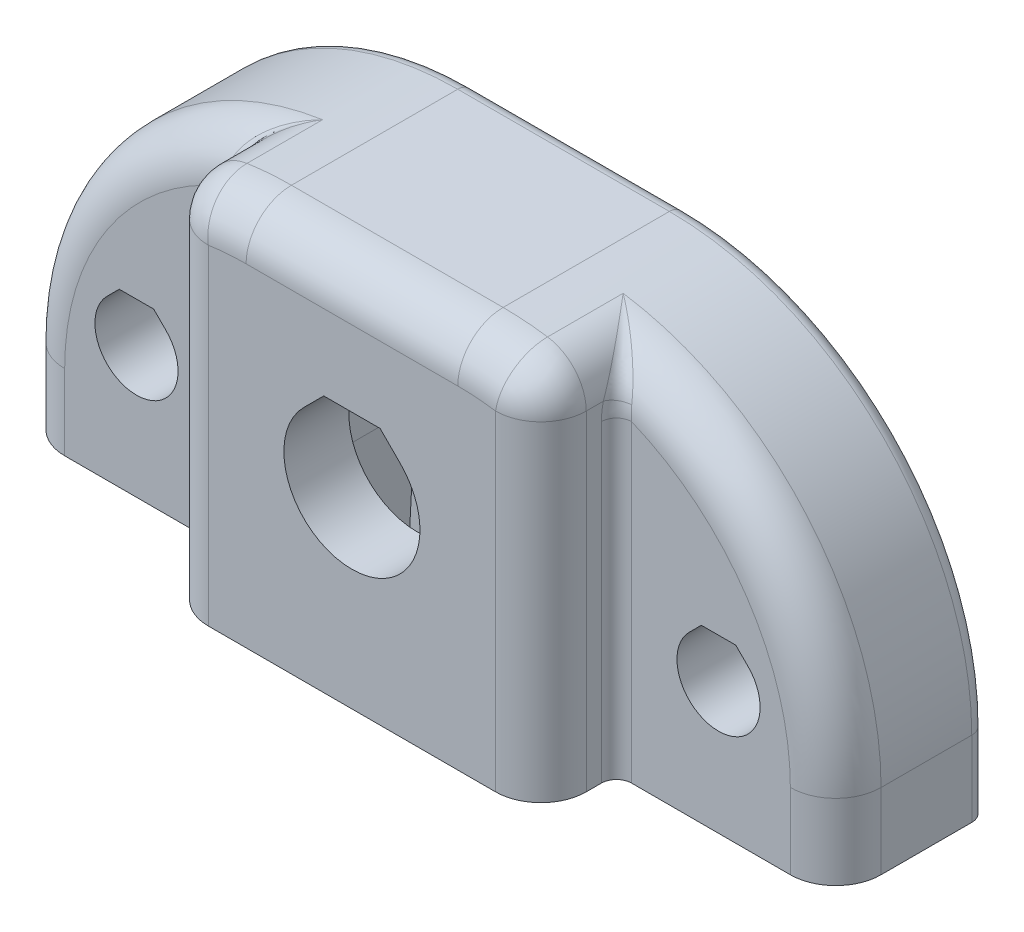
SolidWorks part; units mm, degrees
ref_plane "Front Plane" through (0, 0, 0) normal (0, 0, 1) x (1, 0, 0)
ref_plane "Top Plane" through (0, 0, 0) normal (0, 1, 0) x (1, 0, 0)
ref_plane "Right Plane" through (0, 0, 0) normal (1, 0, 0) x (0, 0, -1)
sketch "Sketch1" plane through (0, 0, 0) normal (0, 0, 1) x (1, 0, 0)
  line L0 (-27, -12.5) -> (27, -12.5)
  line L1 (6.5, 3.7528) -> (0, 7.5056) construction
  line L2 (0, 7.5056) -> (-6.5, 3.7528) construction
  line L3 (-6.5, 3.7528) -> (-6.5, -3.7528) construction
  line L4 (-6.5, -3.7528) -> (0, -7.5056) construction
  line L5 (0, -7.5056) -> (6.5, -3.7528) construction
  line L6 (6.5, -3.7528) -> (6.5, 3.7528) construction
  line L7 (-27, -12.5) -> (-27, -7.5)
  line L8 (27, -12.5) -> (27, -7.5)
  line L9 (-7, 12.5) -> (7, 12.5)
  line L10 (-27, -12.5) -> (27, 12.5) construction
  line L11 (27, -12.5) -> (-27, 12.5) construction
  line L12 (3.182, 3.182) -> (1.864, 4.5)
  line L13 (1.864, 4.5) -> (-1.864, 4.5)
  line L14 (-1.864, 4.5) -> (-3.182, 3.182)
  arc A0 (-3.182, 3.182) -> (3.182, 3.182) centre (0, 0) ccw
  circle A1 centre (0, 0) radius 6.5 construction
  arc A2 (27, -7.5) -> (7, 12.5) centre (7, -7.5) ccw
  arc A3 (-7, 12.5) -> (-27, -7.5) centre (-7, -7.5) ccw
  point P22 (0, 4.5)
  dimension "D1" = 9
  dimension "D2" = 13
  dimension "D5" = 20
  dimension "D3" = 54
  dimension "D4" = 25
  dimension "D6" = 90
extrude "Boss-Extrude1" add sketch "Sketch1" along normal mid plane 15
sketch "Sketch2" plane through (0, 0, 0) normal (0, 0, 1) x (1, 0, 0)
  line L0 (-6.5, -3.7528) -> (-6.9584, -12.5)
  line L1 (0, 7.5056) -> (-6.5, 3.7528)
  line L2 (-6.5, 3.7528) -> (-6.5, -3.7528)
  line L3 (-27, -12.5) -> (27, -12.5) construction
  line L4 (6.5, -3.7528) -> (6.9584, -12.5)
  line L5 (6.5, -3.7528) -> (6.5, 3.7528)
  line L6 (6.5, 3.7528) -> (0, 7.5056)
  line L7 (-6.5, -3.7528) -> (0, -7.5056)
  line L8 (0, -7.5056) -> (6.5, -3.7528)
  line L9 (0, 0) -> (0, -12.5) construction
  line L10 (-6.9584, -12.5) -> (6.9584, -12.5)
  circle A0 centre (0, 0) radius 6.5 construction
  dimension "D1" = 13
  dimension "D2" = 3
  dimension "D3" = 3
  dimension "D4" = 8.7472
extrude "Cut-Extrude1" cut sketch "Sketch2" against normal mid plane 6.4
sketch "Sketch3" plane through (0, 0, 7.5) normal (0, 0, 1) x (1, 0, 0)
  line L0 (12.5, -12.5) -> (12.5, 11.7289)
  line L3 (-27, -12.5) -> (27, -12.5) construction
  line L4 (27, -12.5) -> (27, -7.5) construction
  line L5 (27, -12.5) -> (27, -7.5)
  line L6 (27, -12.5) -> (12.5, -12.5)
  line L7 (6.5, -3.7528) -> (6.5, 3.7528) construction
  line L8 (0, 12.5) -> (0, -12.5) construction
  line L10 (7, 12.5) -> (-7, 12.5) construction
  line L11 (-27, -12.5) -> (-12.5, -12.5)
  line L12 (-27, -12.5) -> (-27, -7.5)
  line L13 (-12.5, -12.5) -> (-12.5, 11.7289)
  arc A0 (27, -7.5) -> (7, 12.5) centre (7, -7.5) ccw construction
  arc A1 (27, -7.5) -> (12.5, 11.7289) centre (7, -7.5) ccw
  arc A2 (-27, -7.5) -> (-12.5, 11.7289) centre (-7, -7.5) cw
  dimension "D1" = 6
extrude "Cut-Extrude2" cut sketch "Sketch3" against normal blind 5
sketch "Sketch4" plane through (0, 0, 2.5) normal (0, 0, 1) x (1, 0, 0)
  line L0 (0, 0) -> (0, -18.8563) construction
  line L1 (12.5, -12.5) -> (27, -12.5) construction
  line L2 (12.5, 11.7289) -> (12.5, -12.5) construction
  line L3 (21.1945, -1.9555) -> (20.3891, -1.15)
  line L4 (20.3891, -1.15) -> (18.1109, -1.15)
  line L5 (18.1109, -1.15) -> (17.3055, -1.9555)
  line L6 (-18.1109, -1.15) -> (-17.3055, -1.9555)
  line L7 (-20.3891, -1.15) -> (-18.1109, -1.15)
  line L8 (-21.1945, -1.9555) -> (-20.3891, -1.15)
  arc A0 (17.3055, -1.9555) -> (21.1945, -1.9555) centre (19.25, -3.9) ccw
  arc A1 (-17.3055, -1.9555) -> (-21.1945, -1.9555) centre (-19.25, -3.9) cw
  point P13 (19.25, -1.15)
  dimension "D2" = 6.75
  dimension "D3" = 5.5
  dimension "D1" = 8.6
  dimension "D4" = 90
extrude "Cut-Extrude3" cut sketch "Sketch4" against normal up to next
fillet "Fillet1" radius 3 11 edges at (9.7769, 12.3063, 7.5) (-9.7769, 12.3063, 7.5) (0, 12.5, 7.5) (27, -10, 2.5) (-27, -10, 2.5) (-12.5, -0.3856, 7.5) (12.5, -0.3856, 7.5) (22.9687, 4.5416, 2.5) (12.5, 11.7289, 5) (-22.9687, 4.5416, 2.5) (-12.5, 11.7289, 5)
fillet "Fillet2" radius 1 11 edges at (27, -10, -7.5) (-27, -10, -7.5) (-21.1421, 6.6421, -7.5) (0, 12.5, -7.5) (21.1421, 6.6421, -7.5) (-12.0076, 10.962, 1.6136) (12.0076, 10.962, 1.6136) (-12.5, -1.9571, 2.5) (12.5, -1.9571, 2.5)
